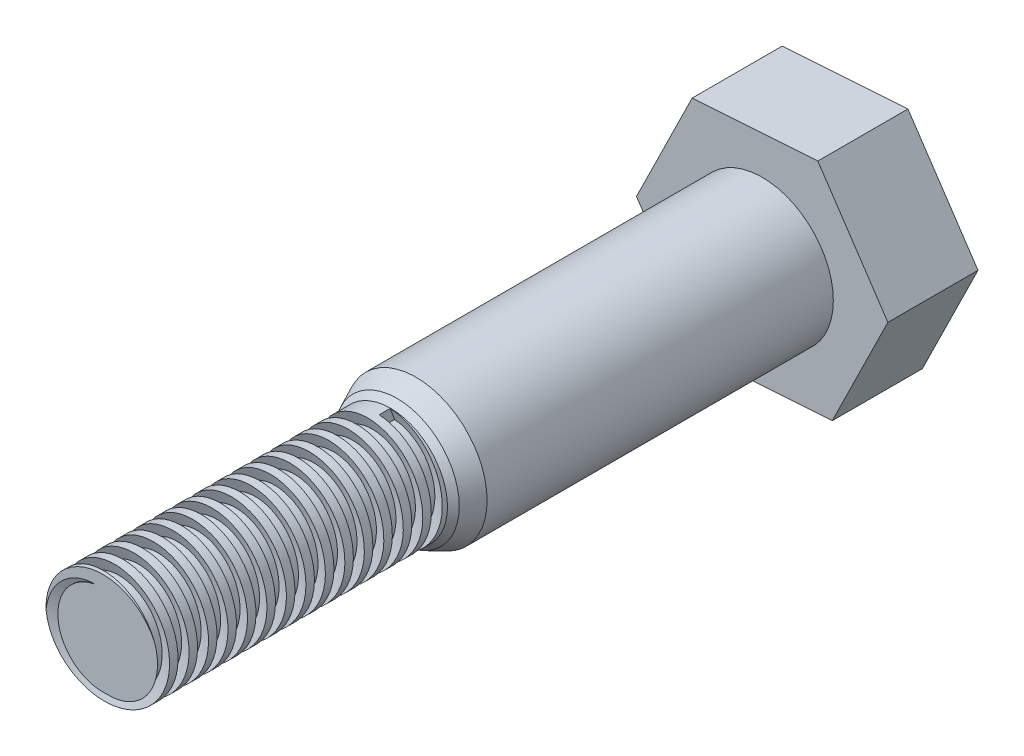
SolidWorks part; units mm, degrees
ref_plane "前视基准面" through (0, 0, 0) normal (0, 0, 1) x (1, 0, 0)
ref_plane "上视基准面" through (0, 0, 0) normal (0, 1, 0) x (1, 0, 0)
ref_plane "右视基准面" through (0, 0, 0) normal (1, 0, 0) x (0, 0, -1)
sketch "草图1" plane through (0, 0, 0) normal (0, 0, 1) x (1, 0, 0)
  circle A0 centre (0, 0) radius 15
  dimension "D1" = 30
extrude "拉伸1" add sketch "草图1" along normal blind 92
sketch "草图2" plane through (0, 0, 0) normal (0, 0, 1) x (1, 0, 0)
  line L1 (14.7707, -22.0717) -> (26.5, 1.7559)
  line L2 (26.5, 1.7559) -> (11.7293, 23.8276)
  line L3 (11.7293, 23.8276) -> (-14.7707, 22.0717)
  line L4 (-14.7707, 22.0717) -> (-26.5, -1.7559)
  line L5 (-26.5, -1.7559) -> (-11.7293, -23.8276)
  line L6 (-11.7293, -23.8276) -> (14.7707, -22.0717)
  circle A0 centre (0, 0) radius 23 construction
  dimension "D1" = 46
  dimension "D2" = 53
extrude "拉伸2" add sketch "草图2" along normal blind 19
sketch "草图7" plane through (0, 0, 92) normal (0, 0, 1) x (1, 0, 0)
  circle A0 centre (0, 0) radius 15
  dimension "D1" = 30
extrude "拉伸4" add sketch "草图7" along normal blind 4 draft 25
sketch "草图22" plane through (0, 0, 96) normal (0, 0, 1) x (1, 0, 0)
  circle A0 centre (0, 0) radius 12
  dimension "D1" = 24
extrude "拉伸22" add sketch "草图22" along normal blind 62
sketch "草图23" plane through (0, 0, 96) normal (0, 0, 1) x (1, 0, 0)
  circle A1 centre (0, 0) radius 13.1348
  dimension "D1" = 26.2695
extrude "拉伸24" add sketch "草图23" along normal blind 2 draft 40
sketch "草图24" plane through (0, 0, 158) normal (0, 0, 1) x (1, 0, 0)
  circle A0 centre (0, 0) radius 12
  dimension "D1" = 24
curve "螺旋线/涡状线1" pitch 4.1071 height 57.5 radius 12 left hand yes centre (0, 0, 158) axis (0, 0, -1) start towards (0, 1, 0)
sketch "草图25" plane through (0, 0, 0) normal (1, 0, 0) x (0, 0, -1)
  line L0 (-158, 21.3795) -> (-158, -24.9516) construction
  line L1 (-97.3524, 12) -> (-97.3524, -12) construction
  line L7 (-154.0018, 9.5) -> (-157, 17.4632)
  line L8 (-157, 17.4632) -> (-160, 17.4632)
  line L9 (-156.0018, 9.5) -> (-154.0018, 9.5)
  line L10 (-160, 17.4632) -> (-156.0018, 9.5)
  dimension "D1" = 60.6476
  dimension "D2" = 1
  dimension "D3" = 3
  dimension "D4" = 2
  dimension "D5" = 2
  dimension "D6" = 6.029
sweep "切除-扫描1" cut profiles "草图25" path "螺旋线/涡状线1" align with end faces yes
sketch "草图26" plane through (0, 0, 0) normal (0, 0, 1) x (1, 0, 0)
  circle A0 centre (0, 0) radius 12
  dimension "D1" = 24
